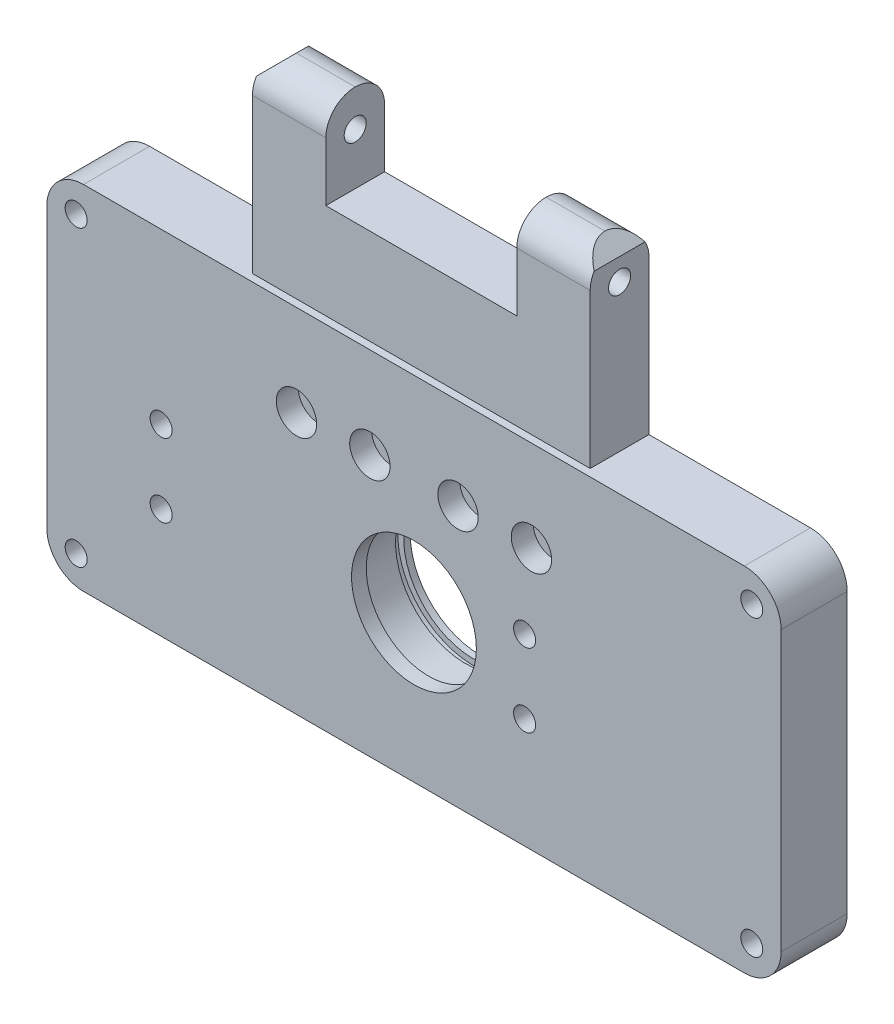
SolidWorks part; units mm, degrees
ref_plane "前视基准面" through (0, 0, 0) normal (0, 0, 1) x (1, 0, 0)
ref_plane "上视基准面" through (0, 0, 0) normal (0, 1, 0) x (1, 0, 0)
ref_plane "右视基准面" through (0, 0, 0) normal (1, 0, 0) x (0, 0, -1)
other "Configuration Table"
sketch "草图2" plane through (0, 0, 0) normal (0, 0, 1) x (1, 0, 0)
  line L1 (-50, 20) -> (50, 20)
  line L2 (-50, 20) -> (-50, -20)
  line L3 (-50, -20) -> (50, -20)
  line L4 (50, 20) -> (50, -20)
  line L5 (-50, 20) -> (50, -20) construction
  line L6 (-50, -20) -> (50, 20) construction
  point P0 (0, 0)
  dimension "D1" = 40
  dimension "D2" = 100
extrude "凸台-拉伸1" add sketch "草图2" along normal blind 6
sketch "草图5" plane through (0, 0, 6) normal (0, 0, 1) x (1, 0, 0)
  line L1 (-50, 20) -> (50, 20)
  line L2 (-50, 20) -> (-50, -20)
  line L3 (-50, -20) -> (50, -20)
  line L4 (50, 20) -> (50, -20)
  line L5 (-50, 20) -> (50, -20) construction
  line L6 (-50, -20) -> (50, 20) construction
  point P0 (0, 0)
  dimension "D1" = 40
  dimension "D2" = 100
extrude "凸台-拉伸2" add sketch "草图5" along normal blind 3
sketch "草图6" plane through (0, 0, 9) normal (0, 0, 1) x (1, 0, 0)
  circle A0 centre (0, 0) radius 9.5
  dimension "D1" = 19
extrude "切除-拉伸1" cut sketch "草图6" against normal blind 7
sketch "草图7" plane through (0, 0, 0) normal (0, 0, -1) x (-1, 0, 0)
  circle A0 centre (0, 0) radius 9.5
  dimension "D1" = 19
extrude "切除-拉伸2" cut sketch "草图7" against normal blind 8
ref_plane "基准面1" through (0, 0, 2) normal (0, 0, 1) x (1, 0, 0)
sketch "草图8" plane through (0, 0, 2) normal (0, 0, 1) x (1, 0, 0)
  circle A0 centre (0, 0) radius 10.3
  dimension "D1" = 20.6
extrude "切除-拉伸3" cut sketch "草图8" against normal blind 1.1
sketch "草图9" plane through (0, 0, 0) normal (0, 0, -1) x (-1, 0, 0)
  circle A0 centre (-15.07, 5) radius 1.5
  circle A1 centre (0, 0) radius 9.5 construction
  circle A2 centre (34.43, 5) radius 1.5
  circle A3 centre (-15.07, -5) radius 1.5
  circle A4 centre (34.43, -5) radius 1.5
  dimension "D1" = 3
  dimension "D2" = 15.07
  dimension "D3" = 5
  dimension "D4" = 2
  dimension "D5" = 2
extrude "切除-拉伸4" cut sketch "草图9" against normal blind 15
sketch "草图11" plane through (0, 20, 0) normal (0, 1, 0) x (1, 0, 0)
  line L1 (-50, 0) -> (50, 0)
  line L2 (-50, 0) -> (-50, -9)
  line L3 (-50, -9) -> (50, -9)
  line L4 (50, 0) -> (50, -9)
extrude "凸台-拉伸5" add sketch "草图11" along normal blind 8
fillet "圆角3" radius 5 4 edges at (-50, -20, 4.5) (50, -20, 4.5) (50, 28, 4.5) (-50, 28, 4.5)
sketch "草图16" plane through (0, 0, 0) normal (0, 0, -1) x (-1, 0, 0)
  line L0 (-45, 28) -> (45, 28) construction
  circle A0 centre (-6, 15.6) radius 1.5
  circle A1 centre (0, 0) radius 9.5 construction
  circle A2 centre (6, 15.6) radius 1.5
  circle A3 centre (-16, 15.6) radius 1.5
  circle A4 centre (16, 15.6) radius 1.5
  dimension "D1" = 3
  dimension "D2" = 12.4
  dimension "D3" = 6
  dimension "D4" = 2
  dimension "D5" = 2
  dimension "D6" = 2
extrude "切除-拉伸6" cut sketch "草图16" against normal blind 10
hole_wizard "孔5" positions "3D草图5" profile "草图19" legacy end condition through all
sketch3d "3D草图5"
  line L0 (-16, 15.6, 9) -> (-16, 15.6, 0) construction
  line L1 (-6, 15.6, 9) -> (-6, 15.6, 0) construction
  line L2 (6, 15.6, 9) -> (6, 15.6, 0) construction
  line L3 (16, 15.6, 9) -> (16, 15.6, 0) construction
  point P0 (-16, 15.6, 9)
  point P4 (-6, 15.6, 9)
  point P8 (6, 15.6, 9)
  point P12 (16, 15.6, 9)
sketch "草图19" plane through (-16, 15.6, 9) normal (1, 0, 0) x (0, -1, 0)
  line L0 (0, 0) -> (0, 9)
  line L1 (0, 9) -> (1.5, 9)
  line L2 (1.5, 9) -> (1.5, 3)
  line L3 (1.5, 3) -> (2.75, 3)
  line L4 (2.75, 3) -> (2.75, 0)
  line L5 (2.75, 0) -> (0, 0)
  line L6 (0, 110) -> (0, -10) construction
  dimension "直径" = 3
  dimension "深度" = 9
  dimension "柱坑直径" = 5.5
  dimension "柱坑深度" = 3
sketch "草图20" plane through (0, 0, 0) normal (0, 0, -1) x (-1, 0, 0)
  line L0 (-50, -15) -> (-50, 23) construction
  line L2 (-45, 28) -> (45, 28) construction
  circle A0 centre (-46, 24) radius 1.5
  circle A1 centre (46, 24) radius 1.5
  circle A2 centre (-46, -16) radius 1.5
  circle A3 centre (46, -16) radius 1.5
  dimension "D1" = 3
  dimension "D2" = 4
  dimension "D3" = 4
  dimension "D4" = 2
  dimension "D5" = 2
extrude "切除-拉伸7" cut sketch "草图20" against normal blind 10
sketch "草图21" plane through (0, 0, 9) normal (0, 0, 1) x (1, 0, 0)
  line L0 (50, -15) -> (50, 23) construction
  line L1 (-50, 38.7735) -> (-22, 38.7735)
  line L2 (-50, 38.7735) -> (-50, -23.6521)
  line L3 (-50, -23.6521) -> (-22, -23.6521)
  line L4 (-22, 38.7735) -> (-22, -23.6521)
  line L5 (50, 38.7735) -> (22, 38.7735)
  line L6 (50, 38.7735) -> (50, -24.7735)
  line L7 (50, -24.7735) -> (22, -24.7735)
  line L8 (22, 38.7735) -> (22, -24.7735)
  line L9 (-50, 23) -> (-50, -15) construction
  dimension "D1" = 28
  dimension "D2" = 28
sketch "草图22" plane through (0, 0, 9) normal (0, 0, 1) x (1, 0, 0)
  circle A0 centre (0, 0) radius 9.5
  circle A1 centre (0, 0) radius 8.5
  dimension "D1" = 19
  dimension "D2" = 17
extrude "凸台-拉伸6" add sketch "草图22" against normal blind 2
sketch "草图23" plane through (0, 28, 0) normal (0, 1, 0) x (1, 0, 0)
  line L0 (0, 0) -> (0, -8) construction
  line L1 (45, 0) -> (-45, 0) construction
  line L4 (23, 0) -> (-23, 0)
  line L6 (23, -8) -> (-23, -8)
  line L7 (-23, 0) -> (-23, -8)
  line L8 (23, 0) -> (23, -8)
  dimension "D1" = 0
  dimension "D2" = 23
  dimension "D3" = 8
extrude "凸台-拉伸7" add sketch "草图23" along normal blind 25
sketch "草图24" plane through (0, 53, 0) normal (0, 1, 0) x (1, 0, 0)
  line L0 (0, 0) -> (0, -8) construction
  line L1 (23, 0) -> (-23, 0) construction
  line L2 (-23, -8) -> (23, -8) construction
  line L3 (13, 0) -> (13, -8)
  line L4 (13, 0) -> (-13, 0)
  line L5 (0, 0) -> (0, -8)
  line L6 (13, -8) -> (-13, -8)
  line L7 (-13, 0) -> (-13, -8)
  line M6 (-23, -8) -> (23, -8)
  line M8 (23, 0) -> (-23, 0)
  dimension "D1" = 13
extrude "切除-拉伸8" cut sketch "草图24" against normal blind 12 contours L4 L7 L5 M6 | L5 L3 M8 M6 region at (6.5, 53, 4) region at (-6.5, 53, 4)
chamfer "倒角1" distance 2 angle 45 2 edges at (23, 53, 4) (-23, 53, 4)
fillet "圆角4" radius 4 4 edges at (17, 53, 8) (17, 53, 0) (-17, 53, 8) (-17, 53, 0)
sketch "草图25" plane through (23, 0, 0) normal (1, 0, 0) x (0, 0, -1)
  line L0 (-8, 28) -> (0, 28) construction
  line L1 (-4, 28) -> (-4, 53) construction
  line L2 (-8, 28) -> (0, 28) construction
  circle A0 centre (-4, 48) radius 1.5
  point P9 (0, 0)
  dimension "D2" = 3
  dimension "D1" = 20
extrude "切除-拉伸9" cut sketch "草图25" against normal through all
